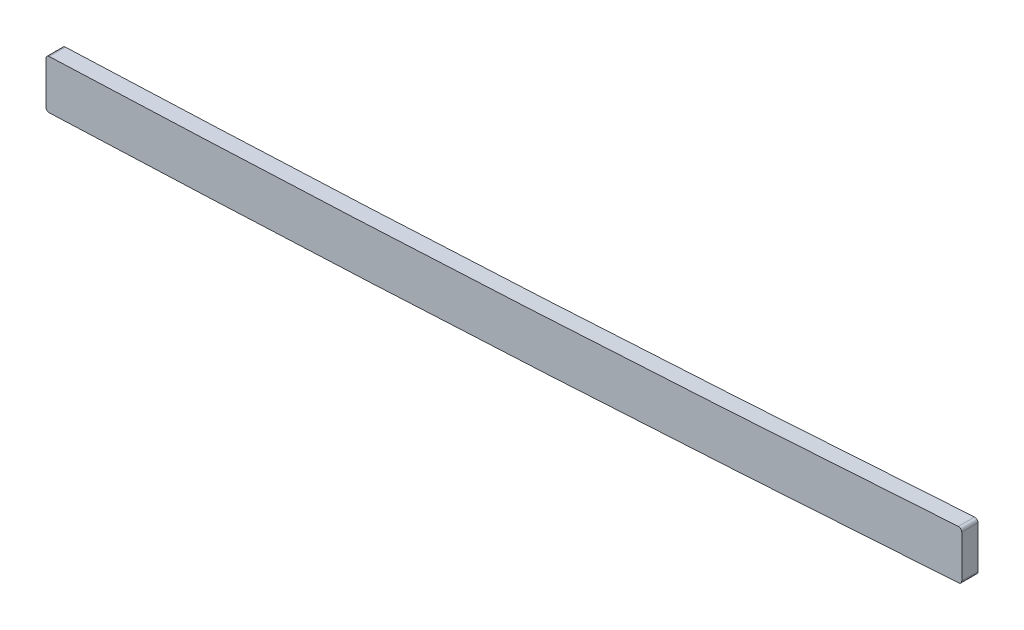
SolidWorks part; units mm, degrees
ref_plane "Front Plane" through (0, 0, 0) normal (0, 0, 1) x (1, 0, 0)
ref_plane "Top Plane" through (0, 0, 0) normal (0, 1, 0) x (1, 0, 0)
ref_plane "Right Plane" through (0, 0, 0) normal (1, 0, 0) x (0, 0, -1)
sketch "Sketch1" plane through (0, 0, 0) normal (0, 0, 1) x (1, 0, 0)
  line L0 (1046.2855, 53.4707) -> (499.61, 53.4707) construction
  line L1 (55, 0) -> (-55, 0) construction
  line L2 (1046.2855, -53.4707) -> (499.61, -53.4707)
  line L3 (1046.2855, -34.4207) -> (499.61, -34.4207)
  line L4 (99.06, -18.1493) -> (99.06, -37.7415)
  line L5 (2669.54, 9.5231) -> (2669.54, -9.569)
  line L6 (2311.4, -9.2457) -> (2311.4, -28.3104)
  spline S0 degree 5 poles (2699.7923, 7.5245) (2639.6368, 11.6572) (2579.4813, 15.4358) (2518.4981, 19.1485) (2436.3555, 23.2524) (2354.213, 26.6315) (2332.5703, 27.481) (2156.2686, 34.3778) (1979.9669, 41.6286) (1824.1143, 52.7713) (1636.9286, 53.5796) (1449.7429, 53.454) (1418.0067, 53.4707) (1324.8993, 53.4707) (1231.7919, 53.4707) (1170.4413, 53.4707) (1108.7841, 53.4707) (1047.1269, 53.4707) (1046.8464, 53.4707) (1046.5659, 53.4707) (1046.2855, 53.4707) knots 100.654805 100.654805 100.654805 100.654805 100.654805 100.654805 130.927897 130.927897 130.927897 141.337055 141.337055 141.337055 218.101815 218.101815 218.101815 233.772059 233.772059 233.772059 264.077723 264.077723 264.077723 264.216209 264.216209 264.216209 264.216209 264.216209 264.216209 weights 1 1 1 1 1 1 1 1 1 1 1 1 1 1 1 1 1 1 1 1 1 construction
  spline S1 degree 5 poles (499.61, 53.4707) (492.1368, 53.4707) (484.7543, 53.4707) (477.443, 53.4707) (448.5166, 53.4707) (419.5901, 53.4707) (398.3681, 53.4707) (355.6475, 53.4707) (312.927, 53.4707) (289.2351, 53.4703) (265.365, 53.4707) (241.4948, 53.4707) (241.4716, 53.4707) (241.4484, 53.4707) (241.4251, 53.4707) knots 19.90683 19.90683 19.90683 19.90683 19.90683 19.90683 23.637897 23.637897 23.637897 34.276546 34.276546 34.276546 46.401341 46.401341 46.401341 46.413154 46.413154 46.413154 46.413154 46.413154 46.413154 weights 1 1 1 1 1 1 1 1 1 1 1 1 1 1 1 construction
  spline S2 degree 5 poles (241.4251, 53.4707) (224.2869, 53.4707) (207.1495, 53.4673) (190.2039, 52.6866) (151.6561, 49.0319) (113.1083, 41.5037) (91.9499, 36.3426) (71.313, 30.9696) (50.6762, 24.7565) knots 0 0 0 0 0 0 8.713816 8.713816 8.713816 19.90683 19.90683 19.90683 19.90683 19.90683 19.90683 weights 1 1 1 1 1 1 1 1 1 construction
  spline S3 degree 5 poles (241.4251, -53.4707) (224.2869, -53.4707) (207.1495, -53.4673) (190.2039, -52.6866) (151.6561, -49.0319) (113.1083, -41.5037) (91.9499, -36.3426) (71.313, -30.9696) (50.6762, -24.7565) knots 0 0 0 0 0 0 8.713816 8.713816 8.713816 19.90683 19.90683 19.90683 19.90683 19.90683 19.90683 weights 1 1 1 1 1 1 1 1 1
  spline S4 degree 5 poles (499.61, -53.4707) (492.1368, -53.4707) (484.7543, -53.4707) (477.443, -53.4707) (448.5166, -53.4707) (419.5901, -53.4707) (398.3681, -53.4707) (355.6475, -53.4707) (312.927, -53.4707) (289.2351, -53.4703) (265.365, -53.4707) (241.4948, -53.4707) (241.4716, -53.4707) (241.4484, -53.4707) (241.4251, -53.4707) knots 19.90683 19.90683 19.90683 19.90683 19.90683 19.90683 23.637897 23.637897 23.637897 34.276546 34.276546 34.276546 46.401341 46.401341 46.401341 46.413154 46.413154 46.413154 46.413154 46.413154 46.413154 weights 1 1 1 1 1 1 1 1 1 1 1 1 1 1 1
  spline S5 degree 5 poles (2699.7923, -7.5245) (2639.6368, -11.6572) (2579.4813, -15.4358) (2518.4981, -19.1485) (2436.3555, -23.2524) (2354.213, -26.6315) (2332.5703, -27.481) (2156.2686, -34.3778) (1979.9669, -41.6286) (1824.1143, -52.7713) (1636.9286, -53.5796) (1449.7429, -53.454) (1418.0067, -53.4707) (1324.8993, -53.4707) (1231.7919, -53.4707) (1170.4413, -53.4707) (1108.7841, -53.4707) (1047.1269, -53.4707) (1046.8464, -53.4707) (1046.5659, -53.4707) (1046.2855, -53.4707) knots 100.654805 100.654805 100.654805 100.654805 100.654805 100.654805 130.927897 130.927897 130.927897 141.337055 141.337055 141.337055 218.101815 218.101815 218.101815 233.772059 233.772059 233.772059 264.077723 264.077723 264.077723 264.216209 264.216209 264.216209 264.216209 264.216209 264.216209 weights 1 1 1 1 1 1 1 1 1 1 1 1 1 1 1 1 1 1 1 1 1
  spline S6 degree 1 poles (2698.4867, 11.4807) (1046.2855, -34.4207) knots 0 0 1 1 construction
  spline S7 degree 1 poles (499.61, -34.4207) (241.4252, -34.4207) knots 0 0 1 1 construction
  spline S8 degree 1 poles (241.4252, -34.4207) (56.168, -6.5153) knots 0 0 1 1 construction
  spline S9 degree 3 poles (2698.4867, 11.4807) (2691.2474, 10.9833) (2679.1952, 10.1655) (2662.2765, 9.0388) (2635.6663, 7.2925) (2596.8577, 4.8261) (2545.7297, 1.7583) (2494.4053, -1.0986) (2451.533, -3.2666) (2417.1983, -4.8671) (2391.4571, -6.0036) (2365.6347, -7.0869) (2341.0156, -8.0785) (2320.7508, -8.8784) (2303.4475, -9.5581) (2284.7601, -10.2922) (2261.7633, -11.201) (2227.2853, -12.5838) (2184.1756, -14.3661) (2132.4291, -16.6074) (2063.4255, -19.7089) (1977.1749, -23.7005) (1873.7325, -28.1494) (1770.3746, -31.6575) (1667.0857, -33.7931) (1581.0111, -34.3832) (1512.074, -34.4278) (1443.0615, -34.4095) (1356.8009, -34.4244) (1218.7946, -34.4185) (1115.289, -34.4207) (1046.2855, -34.4207) knots 100.654805 100.654805 100.654805 100.654805 102.842388 104.300777 105.766098 110.877392 115.988686 121.09998 126.211274 128.766921 131.322568 133.878215 136.433862 138.55769 139.835514 141.545156 144.100803 146.656449 151.767743 156.879037 161.990331 172.212919 182.435507 192.658094 202.880682 213.10327 218.214564 223.325858 233.548445 243.771033 264.216209 264.216209 264.216209 264.216209
  spline S10 degree 3 poles (499.61, -34.4207) (488.6147, -34.4207) (472.2364, -34.4207) (449.9402, -34.4207) (427.7713, -34.4207) (405.8747, -34.4207) (384.5849, -34.4207) (368.9002, -34.4207) (353.3766, -34.4207) (332.6085, -34.4207) (306.2878, -34.4206) (274.0235, -34.4205) (252.271, -34.4207) (241.4252, -34.4207) knots 19.90683 19.90683 19.90683 19.90683 23.22012 24.876765 26.533411 29.846701 31.503346 33.159992 34.816637 36.473282 39.786573 43.099863 46.413154 46.413154 46.413154 46.413154
  spline S11 degree 3 poles (241.4252, -34.4207) (239.3949, -34.4207) (235.3223, -34.4205) (227.2744, -34.3987) (217.3194, -34.2975) (205.5307, -33.9764) (189.9633, -33.2126) (170.697, -31.5435) (147.5333, -28.3144) (125.4828, -24.2021) (107.4399, -20.1965) (92.2061, -16.4882) (75.9505, -12.2555) (63.6202, -8.7589) (56.168, -6.5153) knots 0 0 0 0 0.622088 1.244177 2.488354 3.732531 4.976707 7.465061 9.953415 12.441768 14.558235 15.802412 17.418476 19.90683 19.90683 19.90683 19.90683
  point P2 (0, 0)
  dimension "D1" = 50.6762
  dimension "D3" = 99.06
  dimension "D4" = 2669.54
  dimension "D5" = 2311.4
  dimension "D2" = 19.05
extrude "Boss-Extrude1" add sketch "Sketch1" along normal mid plane 6.35 contours L5 S9 L6 S5 region at (2490.5174, -10.3074, 0)
fillet "Fillet1" radius 1.27 4 edges at (2669.54, 9.5231, 0) (2311.4, -9.2457, 0)
